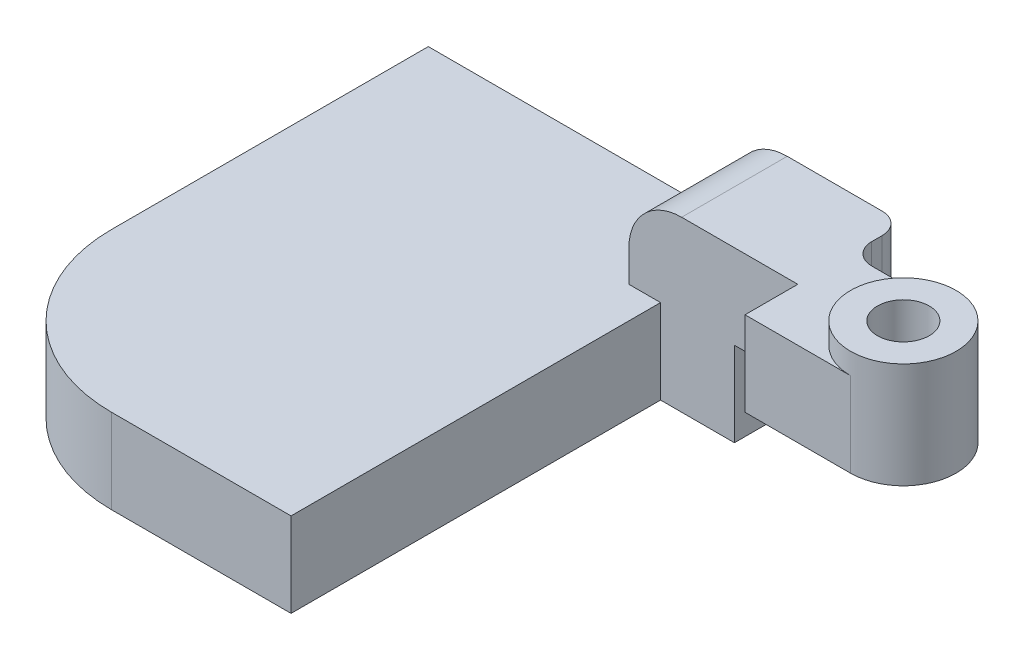
SolidWorks part; units mm, degrees
ref_plane "前视基准面" through (0, 0, 0) normal (0, 0, 1) x (1, 0, 0)
ref_plane "上视基准面" through (0, 0, 0) normal (0, 1, 0) x (1, 0, 0)
ref_plane "右视基准面" through (0, 0, 0) normal (1, 0, 0) x (0, 0, -1)
sketch "草图1" plane through (0, 0, 0) normal (0, 1, 0) x (1, 0, 0)
  line L0 (0, 0) -> (0, 10)
  line L1 (0, 10) -> (-70, 10)
  line L2 (-70, 10) -> (-70, -40)
  line L3 (-70, -40) -> (-25, -40)
  line L4 (-25, -40) -> (-25, 0)
  line L5 (-25, 0) -> (0, 0)
  dimension "D1" = 10
  dimension "D2" = 70
  dimension "60" = 50
  dimension "D4" = 25
extrude "凸台-拉伸1" add sketch "草图1" along normal blind 8
sketch "草图2" plane through (0, 8, 0) normal (0, 1, 0) x (1, 0, 0)
  line L0 (0, 0) -> (0, 10) construction
  line L1 (0, 10) -> (-70, 10) construction
  point P0 (-5, 5)
  dimension "D1" = 5
  dimension "D2" = 5
fillet "圆角1" radius 5 2 edges at (0, 4, 0) (0, 4, -10)
sketch "草图5" plane through (0, 8, 0) normal (0, 1, 0) x (1, 0, 0)
  line L1 (-25, 0) -> (-15, 0)
  line L2 (-25, 0) -> (-25, 5)
  line L3 (-25, 5) -> (-15, 5)
  line L4 (-15, 0) -> (-15, 5)
  dimension "D1" = 10
  dimension "D2" = 5
extrude "切除-拉伸1" cut sketch "草图5" against normal blind 10 contours L3 L4 L1 L2
sketch "草图6" plane through (0, 8, 0) normal (0, 1, 0) x (1, 0, 0)
  line L1 (-70, 10) -> (-15, 10)
  line L2 (-70, 10) -> (-70, 15)
  line L3 (-70, 15) -> (-15, 15)
  line L4 (-15, 10) -> (-15, 15)
  dimension "D1" = 5
  dimension "D2" = 55
extrude "凸台-拉伸2" add sketch "草图6" against normal blind 8
sketch "草图7" plane through (0, 8, 0) normal (0, 1, 0) x (1, 0, 0)
  circle A0 centre (-5, 5) radius 5
extrude "凸台-拉伸3" add sketch "草图7" along normal blind 2
hole_wizard "孔1" positions "草图8" profile "草图9" legacy
sketch "草图8" plane through (0, 10, 0) normal (0, 1, 0) x (1, 0, 0)
  point P0 (-5, 5)
sketch "草图9" plane through (-5, 10, -5) normal (1, 0, 0) x (0, 0, 1)
  line L0 (0, 0) -> (0, 4)
  line L1 (0, 4) -> (2.45, 4)
  line L2 (2.45, 4) -> (2.45, 0)
  line L3 (2.45, 0) -> (0, 0)
  line L4 (0, 110) -> (0, -10) construction
  dimension "直径" = 4.9
  dimension "深度" = 4
hole_wizard "孔2" positions "草图10" profile "草图11" legacy end condition through all
sketch "草图10" plane through (0, 0, 0) normal (0, -1, 0) x (-1, 0, 0)
  point P0 (5, 5)
sketch "草图11" plane through (-5, 0, -5) normal (1, 0, 0) x (0, 0, -1)
  line L0 (0, 0) -> (0, 10)
  line L1 (0, 10) -> (1.5, 10)
  line L2 (1.5, 10) -> (1.5, 0)
  line L3 (1.5, 0) -> (0, 0)
  line L4 (0, 110) -> (0, -10) construction
  dimension "直径" = 3
  dimension "深度" = 10
sketch "草图12" plane through (0, 0, 0) normal (0, -1, 0) x (-1, 0, 0)
  point P0 (5, 5)
hole_wizard "孔3" positions "草图12" profile "草图13" legacy
sketch "草图13" plane through (-5, 0, -5) normal (1, 0, 0) x (0, 0, -1)
  line L0 (0, 0) -> (0, 2)
  line L1 (0, 2) -> (2.25, 2)
  line L2 (2.25, 2) -> (2.25, 0)
  line L3 (2.25, 0) -> (0, 0)
  line L4 (0, 110) -> (0, -10) construction
  dimension "直径" = 4.5
  dimension "深度" = 2
sketch "草图16" plane through (0, 8, 0) normal (0, 1, 0) x (1, 0, 0)
  line L0 (-25, -40) -> (-25, 5) construction
  line L1 (-70, -40) -> (-25, -40)
  line L2 (-70, -40) -> (-70, -30)
  line L3 (-70, -30) -> (-25, -30)
  line L4 (-25, -40) -> (-25, -30)
  dimension "D1" = 10
extrude "切除-拉伸4" cut sketch "草图16" against normal through all
sketch "草图17" plane through (0, 0, 0) normal (0, -1, 0) x (1, 0, 0)
  line L0 (-15, -15) -> (-70, -15) construction
  line L1 (-70, 30) -> (-25, 30)
  line L2 (-70, 30) -> (-70, -15)
  line L3 (-70, -15) -> (-25, -15)
  line L4 (-25, 30) -> (-25, -15)
  line L5 (-25, 30) -> (-25, -5) construction
extrude "凸台-拉伸4" add sketch "草图17" along normal blind 16
sketch "草图20" plane through (0, 8, 0) normal (0, 1, 0) x (1, 0, 0)
  line L1 (-25, -30) -> (-70, -30)
  line L2 (-25, -30) -> (-25, 15)
  line L3 (-25, 15) -> (-70, 15)
  line L4 (-70, -30) -> (-70, 15)
extrude "切除-拉伸5" cut sketch "草图20" against normal blind 8
sketch "草图21" plane through (0, 0, -15) normal (0, 0, -1) x (-1, 0, 0)
  line L1 (15, 0) -> (25, 0)
  line L2 (15, 0) -> (15, -16)
  line L3 (15, -16) -> (25, -16)
  line L4 (25, 0) -> (25, -16)
extrude "凸台-拉伸6" add sketch "草图21" against normal up to surface (10 mm away) up to face at (-20, 4, -5)
sketch "草图22" plane through (0, 0, -10) normal (0, 0, -1) x (-1, 0, 0)
  line L1 (5, 8) -> (15, 8)
  line L2 (5, 8) -> (5, 0)
  line L3 (5, 0) -> (15, 0)
  line L4 (15, 8) -> (15, 0)
sketch "草图23" plane through (0, -16, 0) normal (0, -1, 0) x (1, 0, 0)
  line L1 (-70, 30) -> (-15, 30)
  line L2 (-70, 30) -> (-70, -15)
  line L3 (-70, -15) -> (-15, -15)
  line L4 (-15, 30) -> (-15, -15)
extrude "切除-拉伸6" cut sketch "草图23" against normal blind 8
sketch "草图24" plane through (-25, 0, 0) normal (1, 0, 0) x (0, 0, -1)
  line L1 (-30, 0) -> (5, 0)
  line L2 (-30, 0) -> (-30, -8)
  line L3 (-30, -8) -> (5, -8)
  line L4 (5, 0) -> (5, -8)
extrude "切除-拉伸7" cut sketch "草图24" against normal blind 3
fillet "圆角5" radius 2 2 edges at (-15, 0, -15) (-15, 4, -10)
sketch "草图25" plane through (-70, 0, 0) normal (-1, 0, 0) x (0, 0, 1)
  line L1 (30, 0) -> (-15, 0)
  line L2 (30, 0) -> (30, -8)
  line L3 (30, -8) -> (-15, -8)
  line L4 (-15, 0) -> (-15, -8)
extrude "切除-拉伸8" cut sketch "草图25" against normal blind 10
fillet "圆角6" radius 15 1 edges at (-60, -4, 30)
sketch "草图27" plane through (0, -8, 0) normal (0, -1, 0) x (-1, 0, 0)
  line L0 (60, 15) -> (17, 15) construction
  line L1 (15, 5) -> (21, 5)
  line L2 (15, 5) -> (15, 15)
  line L3 (15, 15) -> (21, 15)
  line L4 (21, 5) -> (21, 15)
  dimension "D1" = 6
extrude "切除-拉伸10" cut sketch "草图27" against normal blind 5
sketch "草图28" plane through (0, 0, -15) normal (0, 0, -1) x (-1, 0, 0)
  line L1 (21, -3) -> (15, -3)
  line L2 (21, -3) -> (21, 0)
  line L3 (21, 0) -> (15, 0)
  line L4 (15, -3) -> (15, 0)
extrude "切除-拉伸11" cut sketch "草图28" against normal through all contours L2 L3 L4 L1
sketch "草图29" plane through (-25, 0, 0) normal (-1, 0, 0) x (0, 0, 1)
  line L1 (-5, 8) -> (-15, 8)
  line L2 (-5, 8) -> (-5, 0)
  line L3 (-5, 0) -> (-15, 0)
  line L4 (-15, 8) -> (-15, 0)
extrude "凸台-拉伸7" add sketch "草图29" along normal blind 6
fillet "圆角7" radius 5 1 edges at (-31, 8, -10)
